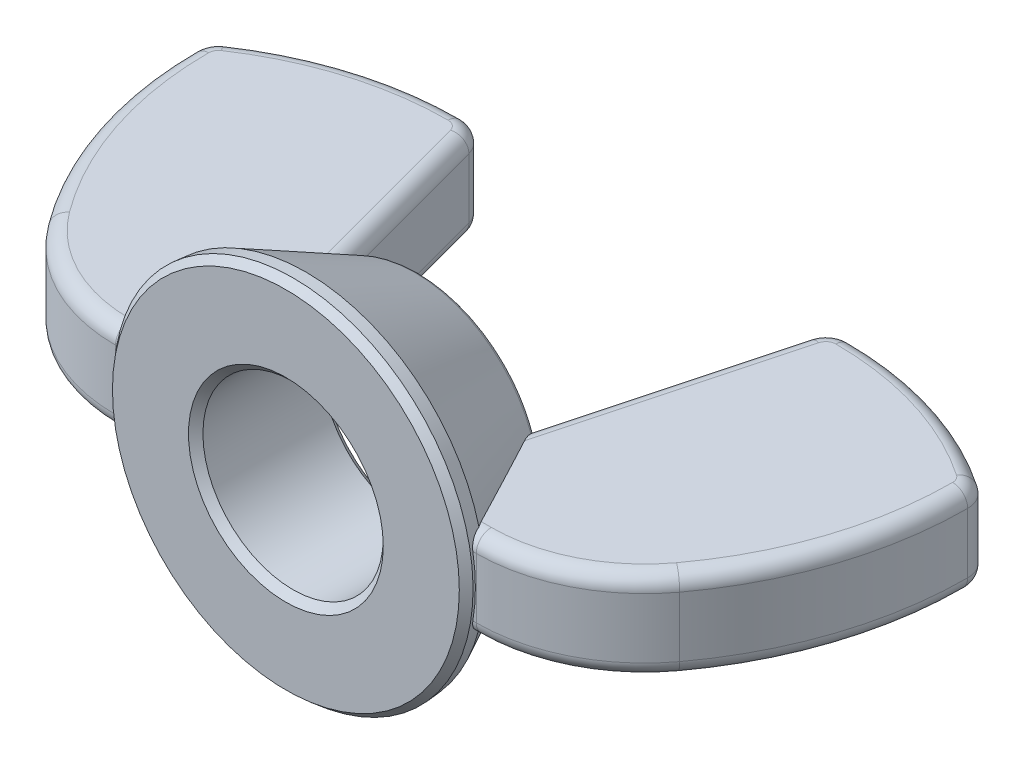
SolidWorks part; units mm, degrees
ref_plane "Front Plane" through (0, 0, 0) normal (0, 0, 1) x (1, 0, 0)
ref_plane "Top Plane" through (0, 0, 0) normal (0, 1, 0) x (1, 0, 0)
ref_plane "Right Plane" through (0, 0, 0) normal (1, 0, 0) x (0, 0, -1)
sketch "Sketch1" plane through (0, 0, 0) normal (0, 0, 1) x (1, 0, 0)
  circle A0 centre (0, 0) radius 2.5
  circle A1 centre (0, 0) radius 5
  dimension "C" = 10
sketch "Sketch2" plane through (0, 0, 0) normal (0, 1, 0) x (1, 0, 0)
  line L0 (0, 0) -> (0, 10.29) construction
  line L1 (-2.5, 0) -> (2.5, 0) construction
  line L2 (-10.73, 10.29) -> (10.73, 10.29) construction
  line L3 (10.73, 10.29) -> (10.73, 0) construction
  line L4 (-10.73, 10.29) -> (-10.73, 0) construction
  line L5 (-10.73, 0) -> (10.73, 0) construction
  line L6 (-3.4165, 3.7044) -> (3.4165, 3.7044) construction
  line L7 (0, 0) -> (0, 3.7044) construction
  line L8 (-4.3144, 0.5557) -> (5, 0.5557) construction
  line L9 (5, 0) -> (5, 3.7044) construction
  line L10 (3.0748, 3.7044) -> (4.8876, 10.4699)
  line L12 (3.4165, 3.7044) -> (3.4165, 0.2778) construction
  line L13 (-5, 0) -> (5, 0) construction
  line L14 (5, 0.5557) -> (3.4165, 3.7044) construction
  line L15 (4.8876, 10.4699) -> (11.019, 8.5954)
  line L16 (11.019, 8.5954) -> (6.9252, 0.2778)
  line L17 (5, 0.2778) -> (6.9252, 0.2778)
  line L19 (3.0748, 0.2778) -> (5, 0.2778)
  line L20 (-3.0748, 3.7044) -> (3.0748, 3.7044) construction
  line L21 (3.0748, 3.7044) -> (3.0748, 0.2778)
  line L22 (-5, 0) -> (5, 0) construction
  circle A3 centre (10.0356, 8.1699) radius 0.6944 construction
  circle A4 centre (5.3723, 9.5956) radius 0.6944 construction
  dimension "D6" = 1.3889
  dimension "D2" = 3.7044
  dimension "D4" = 6.8329
  dimension "D1" = 0.5557
  dimension "D3" = 26.698
  dimension "D5" = 0.2778
  dimension "D8" = 17
  dimension "D9" = 6.1496
  dimension "D7" = 15
  dimension "D10" = 10
sketch "Sketch13" plane through (0, 0, 0) normal (0, 1, 0) x (1, 0, 0)
  line L1 (3.0748, 3.7044) -> (3.0748, 0.2778) construction
  line L2 (3.0748, 3.7044) -> (4.8876, 10.4699) construction
  line L3 (-10.73, 10.29) -> (10.73, 10.29) construction
  line L4 (10.73, 10.29) -> (10.73, 0) construction
  line L5 (5, 0.2778) -> (6.9252, 0.2778) construction
  line L6 (3.0748, 0.2778) -> (5, 0.2778) construction
  line L7 (0, 0) -> (0, 3.7044) construction
  line L8 (-2.5, 0) -> (2.5, 0) construction
  line L9 (0, 0) -> (0, 10.29) construction
  line L10 (-3.4165, 3.7044) -> (3.4165, 3.7044) construction
  line L11 (3.0748, 0.2778) -> (5, 0.2778)
  line L12 (3.0748, 3.7044) -> (3.0748, 0.2778)
  line L13 (3.0748, 3.7044) -> (4.7015, 9.7753)
  circle A0 centre (10.0356, 8.1699) radius 0.6944 construction
  circle A1 centre (5.3723, 9.5956) radius 0.6944 construction
  arc A5 (10.73, 8.1699) -> (10.4239, 8.7456) centre (10.0356, 8.1699) ccw
  arc A6 (5.3723, 10.29) -> (4.7015, 9.7753) centre (5.3723, 9.5956) ccw
  arc A7 (8.7493, 2.1668) -> (10.73, 8.1699) centre (0.6427, 8.1699) ccw
  arc A8 (10.4239, 8.7456) -> (5.3723, 10.29) centre (5.3723, 1.2563) ccw
  arc A10 (5, 0.2778) -> (8.7493, 2.1668) centre (5, 4.9432) ccw
extrude "Extrude2" add sketch "Sketch13" along normal mid plane 2.5
sketch "Sketch3" plane through (0, 0, 0) normal (0, 0, 1) x (1, 0, 0)
  circle A0 centre (0, 0) radius 5 construction
  circle A1 centre (0, 0) radius 5
extrude "Extrude1" add sketch "Sketch3" against normal up to vertex (0.5557 mm away) draft 5 separate body up to point (5, 0, -0.5557)
sketch "Sketch15" plane through (0, 0, -0.5557) normal (0, 0, -1) x (-1, 0, 0)
  circle A1 centre (0, 0) radius 4.9514
  circle A2 centre (0, 0) radius 4.9514
  dimension "D1" = 0
extrude "Extrude3" add sketch "Sketch15" along normal up to vertex (3.1487 mm away) draft 26.698 up to point (0, 0, -3.7044)
fillet "Fillet3" radius 0.254 1 edges at (-3.3678, 0, -3.7044)
sketch "Sketch12" plane through (0, 0, -3.7044) normal (0, 0, -1) x (-1, 0, 0)
  circle A1 centre (0, 0) radius 4.9514
  circle A2 centre (0, 0) radius 4.9514 construction
  dimension "D1" = 9.9028
sketch "Sketch4" plane through (0, 0, 0) normal (0, 0, 1) x (1, 0, 0)
  circle A0 centre (0, 0) radius 2.5 construction
  circle A1 centre (0, 0) radius 2.5
extrude "Cut-Extrude1" cut sketch "Sketch4" against normal through all
sketch "Sketch5" plane through (0, 0, 0) normal (0, 0, 1) x (1, 0, 0)
  circle A0 centre (0, 0) radius 2.5 construction
  circle A1 centre (0, 0) radius 2.5
curve "Helix/Spiral1" pitch 0.8 height 5.7044 turns 7.1305 parameters "pitch"=0.8
sketch "Sketch6" plane through (0, 0, 0) normal (0, 1, 0) x (1, 0, 0)
  line L0 (-2.5, -0.7) -> (-1.9804, -0.4)
  line L1 (-1.9804, -0.4) -> (-1.9804, -0.3)
  line L2 (-1.9804, -0.3) -> (-2.5, 0)
  line L3 (-2.5, -0.7) -> (-2.5, 0)
  line L4 (-2.5, -0.35) -> (-1.9804, -0.35) construction
  line L5 (-2.2402, -0.55) -> (-2.2402, -0.15) construction
  line L6 (-2.5, 0) -> (2.5, 0) construction
  dimension "D1" = 60
  dimension "D2" = 0.1
  dimension "D3" = 0.4
sweep "Sweep1" add profiles "Sketch6" path "Helix/Spiral1"
sketch "Sketch7" plane through (0, 0, 0) normal (0, 0, 1) x (1, 0, 0)
  circle A1 centre (0, 0) radius 5
  circle A2 centre (0, 0) radius 5
  dimension "D1" = 0
extrude "Cut-Extrude2" cut sketch "Sketch7" along normal through all
ref_plane "Plane1" through (0, 0, -3.7044) normal (0, 0, 1) x (1, 0, 0)
sketch "Sketch8" plane through (0, 0, -3.7044) normal (0, 0, 1) x (1, 0, 0)
  circle A0 centre (0, 0) radius 4.9514 construction
  circle A2 centre (0, 0) radius 4.9514
extrude "Cut-Extrude3" cut sketch "Sketch8" against normal through all
sketch "Sketch9" plane through (0, 0, 0) normal (0, 0, 1) x (1, 0, 0)
  circle A1 centre (0, 0) radius 2.5
  circle A2 centre (0, 0) radius 2.5
  dimension "D1" = 0
extrude "Cut-Extrude4" cut sketch "Sketch9" against normal through all draft 45
sketch "Sketch11" plane through (0, 0, -3.7044) normal (0, 0, 1) x (1, 0, 0)
  circle A0 centre (0, 0) radius 2.5 construction
  circle A1 centre (0, 0) radius 2.4492
  circle A2 centre (0, 0) radius 2.5 construction
  dimension "D1" = 0.0508
extrude "Cut-Extrude5" cut sketch "Sketch11" along normal through all draft 45
chamfer "Chamfer1" distance 0.2084 angle 45 1 edges at (5, 0, 0)
fillet "Fillet4" radius 0.4167 14 edges at (4.0374, 1.25, -0.2778) (7.0991, 1.25, -0.7767) (4.9495, 1.25, -10.1465) (8.0135, 1.25, -9.8953) (10.6487, 1.25, -8.4959) (4.0374, -1.25, -0.2778) (7.0991, -1.25, -0.7767) (4.9495, -1.25, -10.1465) (8.0135, -1.25, -9.8953) (10.6487, -1.25, -8.4959) (10.222, 1.25, -5.0092) (10.222, -1.25, -5.0092) (3.8882, 1.25, -6.7398) (3.8882, -1.25, -6.7398)
mirror "Mirror6" about plane through (0, 0, 0) normal (1, 0, 0) of bodies 108 113
combine bodies "Combine2" operation type add bodies to combine 116 108 107
sketch "Sketch16" plane through (0, 0, 0) normal (0, 1, 0) x (1, 0, 0)
  line L0 (-5, 0) -> (5, 0)
  dimension "D1" = 10
sketch "Sketch18" plane through (0, 0, -3.7044) normal (0, 0, -1) x (-1, 0, 0)
  circle A0 centre (0, 0) radius 3.2113
extrude "Boss-Extrude3" add sketch "Sketch18" against normal up to surface (3.7044 mm away) up to face at (4.8077, 0, 0)
sketch "Sketch19" plane through (0, 0, -3.7044) normal (0, 0, -1) x (-1, 0, 0)
  circle A0 centre (0, 0) radius 2.5
  dimension "D1" = 5
extrude "Cut-Extrude6" cut sketch "Sketch19" against normal up to surface (3.7044 mm away) up to face at (4.8077, 0, 0)
chamfer "Chamfer2" distance 0.2 angle 45 2 edges at (-2.5, 0, -3.7044) (2.5, 0, 0)
equation "\"D2@Sketch2\" = \"B@Sketch2\"*.36"
equation "\"D3@Helix/Spiral1\" = \"D2@Sketch2\"+2"
equation "\"D2@Sketch6\" = \"pitch@Helix/Spiral1\"*.125"
equation "\"D3@Sketch6\" = \"pitch@Helix/Spiral1\"*.5"
equation "\"D4@Sketch2\" = \"D1@Sketch12\"*.69"
equation "\"D1@Extrude2\" = \"C@Sketch1\"*.25"
equation "\"D1@Sketch2\" = \"D2@Sketch2\"*.150"
equation "\"D5@Sketch2\" = \"D1@Sketch2\"/2"
equation "\"D3@Extrude3\" = \"D3@Sketch2\""
equation "\"D1@Chamfer1\" = \"D5@Sketch2\"*.75"
equation "\"D9@Sketch2\" = \"D4@Sketch2\"*.9"
equation "\"D6@Sketch2\" = \"D1@Extrude2\"/1.8"
equation "\"D1@Fillet4\" = \"D1@Extrude2\"/6"
equation "\"D10@Sketch2\" = \"C@Sketch1\""
equation "\"D1@Sketch16\" = \"D10@Sketch2\""
